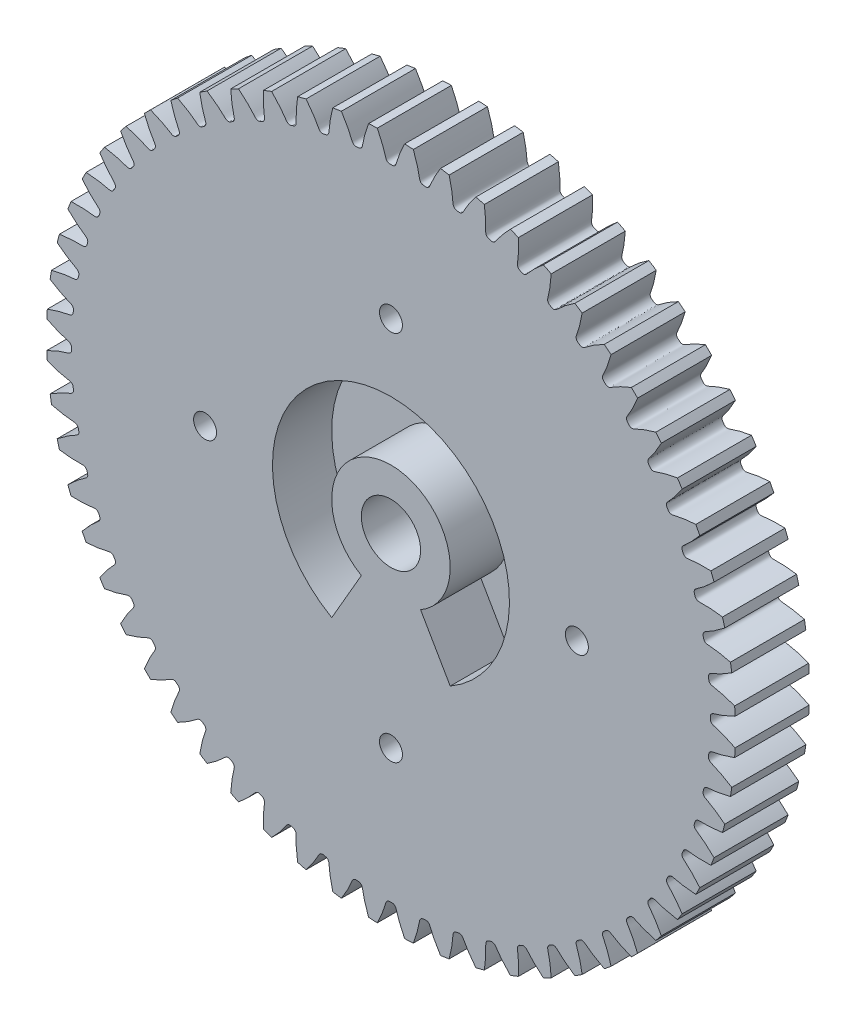
SolidWorks part; units mm, degrees
ref_plane "Front Plane" through (0, 0, 0) normal (0, 0, 1) x (1, 0, 0)
ref_plane "Top Plane" through (0, 0, 0) normal (0, 1, 0) x (1, 0, 0)
ref_plane "Right Plane" through (0, 0, 0) normal (1, 0, 0) x (0, 0, -1)
ref_axis "Axis1" through (0, 0, 5.5) along (0, 0, -1)
sketch "SketchRevolveSpurAssembly01Gear" plane through (0, 0, 0) normal (1, 0, 0) x (0, 0, -1)
  line L0 (0, 0) -> (1, 0) construction
  line L1 (-5, 0) -> (-5, 46.5)
  line L2 (-5, 46.5) -> (5, 46.5)
  line L3 (5, 46.5) -> (5, 0)
  line L4 (5, 0) -> (-5, 0)
  dimension "Side1" = 5
  dimension "OutsideRadius" = 46.5
  dimension "Side2" = 5
revolve "SpurAssembly01Gear" add sketch "SketchRevolveSpurAssembly01Gear" angle 360 about L0
sketch "SketchToothSpurAssembly01Gear" plane through (0, 0, 0) normal (0, 0, 1) x (1, 0, 0)
  arc A0 (46.5369, 1.8824) -> (46.5369, -1.8824) centre (0, 0) cw
  spline S0 degree 3 poles (46.5369, -1.8824) (46.4106, -1.8178) (46.2223, -1.724) (45.9725, -1.6049) (45.7913, -1.5209) (45.614, -1.4411) (45.4406, -1.3655) (45.2713, -1.2938) (45.1061, -1.2261) (44.945, -1.1621) (44.7882, -1.1018) (44.6356, -1.0452) (44.4874, -0.992) (44.3436, -0.9422) (44.2043, -0.8957) (44.0695, -0.8523) (43.9392, -0.8123) (43.7554, -0.7565) (43.5912, -0.7185) (43.4569, -0.6604) (43.397, -0.6284) (43.3333, -0.5856) (43.2647, -0.5249) (43.195, -0.4361) (43.14, -0.3154) (43.1191, -0.1635) (43.1282, 0) (43.1191, 0.1635) (43.14, 0.3154) (43.195, 0.4361) (43.2647, 0.5249) (43.3333, 0.5856) (43.397, 0.6284) (43.4569, 0.6604) (43.5912, 0.7185) (43.7554, 0.7565) (43.9392, 0.8123) (44.0695, 0.8523) (44.2043, 0.8957) (44.3436, 0.9422) (44.4874, 0.992) (44.6356, 1.0452) (44.7882, 1.1018) (44.945, 1.1621) (45.1061, 1.2261) (45.2713, 1.2938) (45.4406, 1.3655) (45.614, 1.4411) (45.7913, 1.5209) (45.9725, 1.6049) (46.2223, 1.724) (46.4106, 1.8178) (46.5369, 1.8824) knots 0 0 0 0 0.051766 0.076686 0.100963 0.124598 0.147592 0.169943 0.191651 0.212718 0.233143 0.252925 0.272065 0.290563 0.308419 0.325633 0.342204 0.358133 0.395729 0.403327 0.411415 0.420483 0.431261 0.444675 0.461387 0.478965 0.5 0.521035 0.538613 0.555325 0.568739 0.579517 0.588585 0.596673 0.604271 0.641867 0.657796 0.674367 0.691581 0.709437 0.727935 0.747075 0.766857 0.787282 0.808349 0.830057 0.852408 0.875402 0.899037 0.923314 0.948234 1 1 1 1
extrude "ToothExtrudeCutSpurAssembly01Gear" cut sketch "SketchToothSpurAssembly01Gear" against normal blind 5 and the other way blind 5
pattern_circular "PatternSpurAssembly01Gear" count 60 over 360 about axis through (0, 0, 5.5) along (0, 0, -1) of "ToothExtrudeCutSpurAssembly01Gear"
sketch "AuxiliarySketchSpurAssembly01Gear" plane through (0, 0, 0) normal (0, 0, 1) x (1, 0, 0)
  circle A0 centre (0, 0) radius 45 construction
  circle A1 centre (0, 0) radius 42.2862 construction
  circle A2 centre (0, 0) radius 43.6372 construction
  circle A3 centre (0, 0) radius 46.5 construction
  circle A4 centre (0, 0) radius 43.125 construction
  dimension "PitchDiameter" = 90
  dimension "BaseDiameter" = 84.5723
  dimension "FormDiameter" = 87.2745
  dimension "MajorDiameter" = 93
  dimension "MinorDiameter" = 86.25
sketch "Sketch3" plane through (0, 0, 5) normal (0, 0, 1) x (1, 0, 0)
  circle A0 centre (0, 0) radius 4
sketch "Sketch4" plane through (0, 0, 5) normal (0, 0, 1) x (1, 0, 0)
  line L0 (0, 0) -> (-9.5, -16.4545) construction
  line L1 (0, 0) -> (9.5, -16.4545) construction
  line L2 (-4, -6.9282) -> (-8, -13.8564)
  line L3 (4, -6.9282) -> (8, -13.8564)
  arc A1 (8, -13.8564) -> (-8, -13.8564) centre (0, 0) ccw
  arc A2 (4, -6.9282) -> (-4, -6.9282) centre (0, 0) ccw
sketch "Sketch5" plane through (0, 0, -5) normal (0, 0, -1) x (-1, 0, 0)
  circle A0 centre (0, 0) radius 4
extrude "Cut-Extrude2" cut sketch "Sketch5" against normal blind 18
sketch "Sketch6" plane through (0, 0, -5) normal (0, 0, -1) x (-1, 0, 0)
  circle A0 centre (25.1, 0) radius 1.55
extrude "Cut-Extrude3" cut sketch "Sketch6" against normal blind 10
pattern_circular "CirPattern2" count 4 over 360 about axis through (0, 0, 5.5) along (0, 0, -1) of "Cut-Extrude3"
extrude "Cut-Extrude4" cut sketch "Sketch4" against normal blind 8
